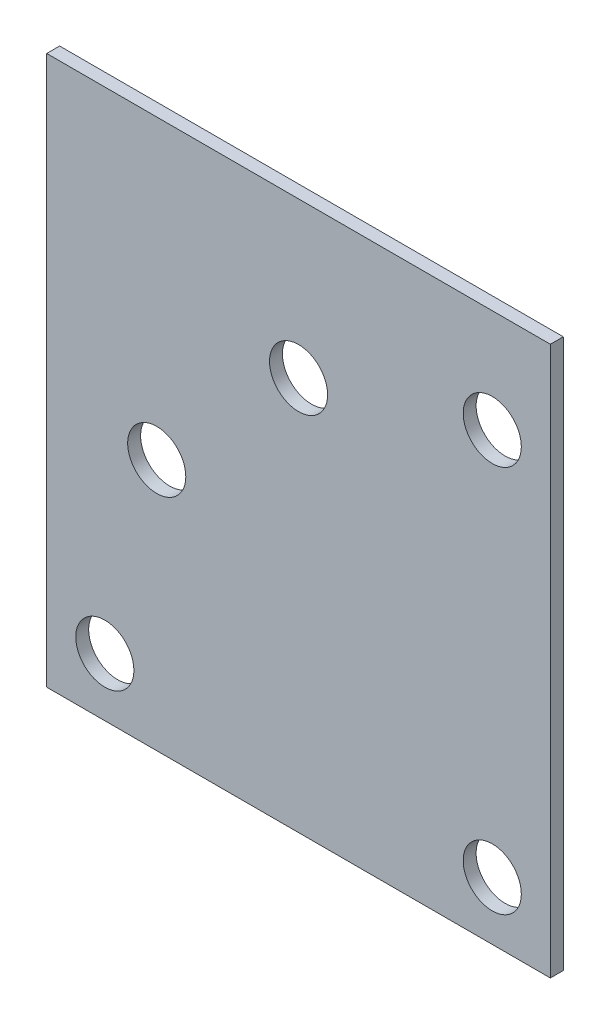
SolidWorks part; units mm, degrees
material "ABS PC"
ref_plane "Front Plane" through (0, 0, 0) normal (0, 0, 1) x (1, 0, 0)
ref_plane "Top Plane" through (0, 0, 0) normal (0, 1, 0) x (1, 0, 0)
ref_plane "Right Plane" through (0, 0, 0) normal (1, 0, 0) x (0, 0, -1)
sketch "Sketch1" plane through (0, 0, 0) normal (0, 0, 1) x (1, 0, 0)
  line L0 (-190.5, 0) -> (0, 0) construction
  line L1 (0, 0) -> (-164.9778, 95.25) construction
  line L2 (-95.25, 164.9778) -> (0, 0) construction
  line L3 (0, 0) -> (0, 190.5) construction
  line L4 (28.575, -28.575) -> (28.575, 241.3)
  line L5 (28.575, -28.575) -> (-219.075, -28.575)
  line L6 (28.575, 241.3) -> (-219.075, 241.3)
  line L7 (-219.075, -28.575) -> (-219.075, 241.3)
  circle A0 centre (0, 0) radius 14.2875
  circle A1 centre (-190.5, 0) radius 14.2875
  circle A2 centre (-164.9778, 95.25) radius 14.2875
  circle A3 centre (-95.25, 164.9778) radius 14.2875
  circle A4 centre (0, 190.5) radius 14.2875
  point P11 (0, 0)
  dimension "D1" = 28.575
  dimension "D2" = 28.575
  dimension "D3" = 28.575
  dimension "D4" = 28.575
  dimension "D5" = 28.575
  dimension "D6" = 190.5
  dimension "D7" = 190.5
  dimension "D8" = 190.5
  dimension "D9" = 190.5
  dimension "D10" = 30
  dimension "D11" = 30
  dimension "D12" = 30
  dimension "D13" = 28.575
  dimension "D14" = 28.575
  dimension "D15" = 50.8
  dimension "D16" = 28.575
extrude "I CAN CHANGE THESE NAMES?!" add sketch "Sketch1" along normal blind 6.35
